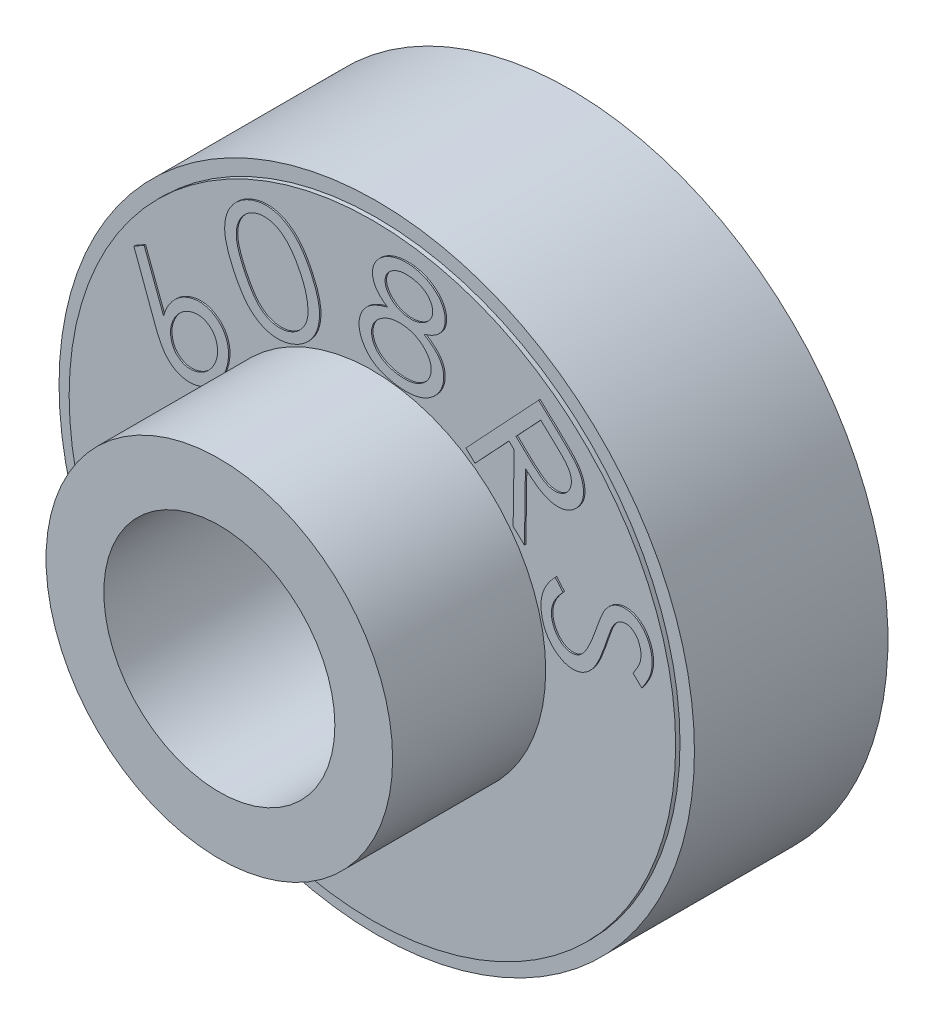
SolidWorks part; units mm, degrees
ref_plane "Front Plane" through (0, 0, 0) normal (0, 0, 1) x (1, 0, 0)
ref_plane "Top Plane" through (0, 0, 0) normal (0, 1, 0) x (1, 0, 0)
ref_plane "Right Plane" through (0, 0, 0) normal (1, 0, 0) x (0, 0, -1)
sketch "Sketch1" plane through (0, 0, 0) normal (0, 0, 1) x (1, 0, 0)
  circle A0 centre (0, 0) radius 11
extrude "Boss-Extrude1" add sketch "Sketch1" along normal blind 7
sketch "Sketch2" plane through (0, 0, 7) normal (0, 0, 1) x (1, 0, 0)
  circle A0 centre (0, 0) radius 4
extrude "Cut-Extrude1" cut sketch "Sketch2" against normal through all
sketch "Sketch3" plane through (0, 0, 7) normal (0, 0, 1) x (1, 0, 0)
  circle A0 centre (0, 0) radius 6
  circle A1 centre (0, 0) radius 4
extrude "Boss-Extrude2" add sketch "Sketch3" along normal blind 5.3
sketch "Sketch4" plane through (0, 0, 7) normal (0, 0, 1) x (1, 0, 0)
  circle A0 centre (0, 0) radius 10.5
  circle A1 centre (0, 0) radius 11
extrude "Cut-Extrude2" cut sketch "Sketch4" against normal blind 0.15
sketch "Sketch5" plane through (0, 0, 0) normal (0, 0, -1) x (-1, 0, 0)
  circle A0 centre (0, 0) radius 21
  circle A1 centre (0, 0) radius 10
extrude "Cut-Extrude3" cut sketch "Sketch5" against normal blind 0.15
sketch "Sketch8" plane through (0, 0, 7) normal (0, 0, 1) x (1, 0, 0)
  circle A0 centre (0, 0) radius 6.4 construction
  text T0 "608RS" font "Century Gothic" height in points 14
extrude "Boss-Extrude3" add sketch "Sketch8" along normal blind 0.05
